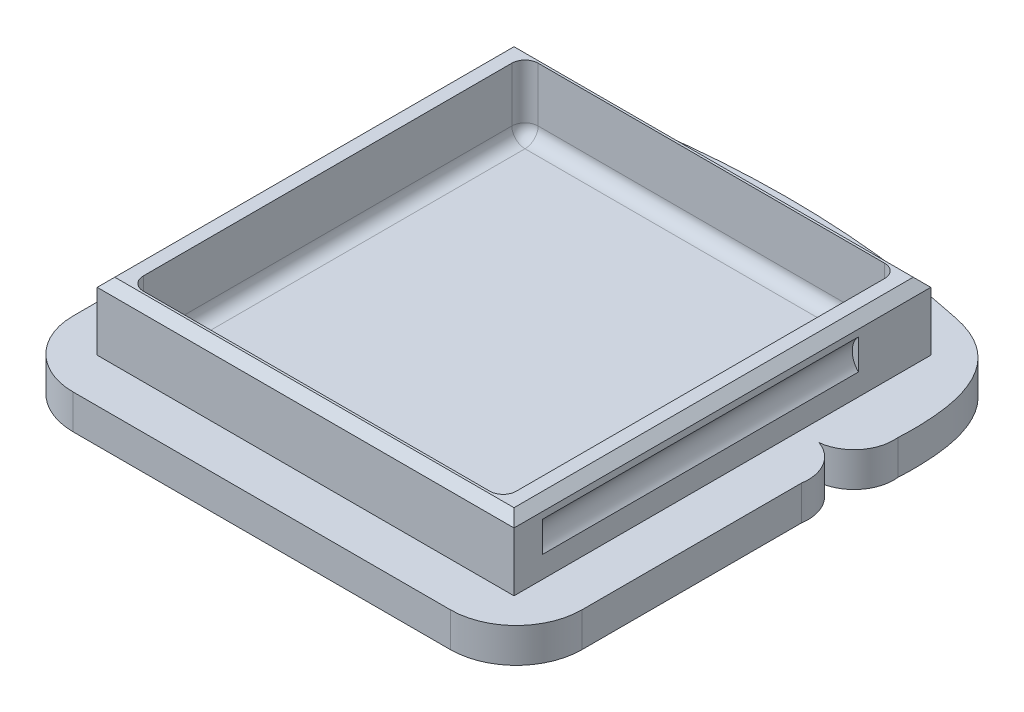
SolidWorks part; units mm, degrees
material "Oak"
ref_plane "Front Plane" through (0, 0, 0) normal (0, 0, 1) x (1, 0, 0)
ref_plane "Top Plane" through (0, 0, 0) normal (0, 1, 0) x (1, 0, 0)
ref_plane "Right Plane" through (0, 0, 0) normal (1, 0, 0) x (0, 0, -1)
sketch "Sketch2" plane through (0, 0, 0) normal (0, 1, 0) x (1, 0, 0)
  line L0 (-66.04, 22.225) -> (66.04, 22.225)
  line L1 (63.5, -66.675) -> (-63.5, -66.675)
  line L2 (63.5, -66.675) -> (63.5, 66.675)
  line L3 (63.5, 66.675) -> (-63.5, 66.675)
  line L4 (-63.5, -66.675) -> (-63.5, 66.675)
  line L5 (63.5, -66.675) -> (-63.5, 66.675) construction
  line L6 (63.5, 66.675) -> (-63.5, -66.675) construction
  line L7 (-73.66, 9.525) -> (-73.66, -53.975)
  line L8 (-54.61, -73.025) -> (54.61, -73.025)
  line L9 (73.66, -53.975) -> (73.66, 9.525)
  line L10 (-73.66, 9.525) -> (-73.66, 13.1711)
  arc A0 (-73.66, 9.525) -> (-66.04, 22.225) centre (-62.3051, 11.348) cw
  arc A1 (73.66, 9.525) -> (66.04, 22.225) centre (62.3051, 11.348) ccw
  arc A2 (-66.04, 22.225) -> (-76.2, 34.925) centre (-64.77, 33.655) cw
  arc A3 (66.04, 22.225) -> (76.2, 34.925) centre (64.77, 33.655) ccw
  arc A4 (-54.2615, 73.3341) -> (54.2615, 73.3341) centre (0, -178.2209) cw
  arc A5 (73.66, -53.975) -> (54.61, -73.025) centre (54.61, -53.975) cw
  arc A6 (-73.66, -53.975) -> (-54.61, -73.025) centre (-54.61, -53.975) ccw
  spline S0 degree 2 poles (-54.2615, 73.3341) (-78.0337, 68.7721) (-76.2, 34.925) knots 0 0 0 1 1 1
  spline S1 degree 2 poles (54.2615, 73.3341) (78.0337, 68.7721) (76.2, 34.925) knots 0 0 0 1 1 1
  point P0 (0, 0)
  dimension "D11" = 11.5003
  dimension "D12" = 11.5003
  dimension "D14" = 11.5003
  dimension "D15" = 11.5003
  dimension "D17" = 19.05
  dimension "D1" = 133.35
  dimension "D2" = 127
  dimension "D3" = 44.45
  dimension "D4" = 2.54
  dimension "D5" = 2.54
  dimension "D6" = 10.16
  dimension "D7" = 10.16
  dimension "D8" = 6.35
  dimension "D9" = 12.7
  dimension "D10" = 12.7
  dimension "D13" = 12.7
extrude "Boss-Extrude1" add sketch "Sketch2" along normal blind 10 contours L7 A6 L8 A5 L9 A1 L0 L2 L1 L4 A0 L10 | L4 L1 L2 L0 | L4 L0 L2 | A2 L0 L4 L10 | S1 A4 S0 L10 L4 L3 L2 | L4 L2 L3 | L0 A3 L2 region at (-72.4781, 0, -27.4885) region at (-64.77, 0, -20.4695) region at (0, 0, -44.45) region at (0, 0, 22.225)
sketch "Sketch3" plane through (0, 10, 0) normal (0, 1, 0) x (1, 0, 0)
  line L1 (-53.975, 57.15) -> (53.975, 57.15)
  line L2 (-53.975, 57.15) -> (-53.975, -57.15)
  line L3 (-53.975, -57.15) -> (53.975, -57.15)
  line L4 (53.975, 57.15) -> (53.975, -57.15)
  line L5 (-53.975, 57.15) -> (53.975, -57.15) construction
  line L6 (-53.975, -57.15) -> (53.975, 57.15) construction
  line L8 (-60.325, 60.325) -> (60.325, 60.325)
  line L9 (-60.325, 60.325) -> (-60.325, -60.325)
  line L10 (-60.325, -60.325) -> (60.325, -60.325)
  line L11 (60.325, 60.325) -> (60.325, -60.325)
  line L12 (-60.325, 60.325) -> (60.325, -60.325) construction
  line L13 (-60.325, -60.325) -> (60.325, 60.325) construction
  point P0 (0, 0)
  point P10 (0, 0)
  dimension "D1" = 107.95
  dimension "D2" = 114.3
  dimension "D3" = 6.35
  dimension "D4" = 3.175
extrude "Boss-Extrude2" add sketch "Sketch3" along normal blind 19.558
fillet "Fillet2" radius 3.81 4 edges at (53.975, 10, 0) (0, 10, -57.15) (-53.975, 10, 0) (0, 10, 57.15)
sketch "Sketch5" plane through (0, 0, 0) normal (0, 0, 1) x (1, 0, 0)
  line L2 (60.325, 25.0747) -> (60.325, 16.2613)
  line L4 (-60.325, 25.0747) -> (-60.325, 16.2613)
  arc A0 (60.325, 25.0747) -> (60.325, 16.2613) centre (64.897, 20.668) ccw
  arc A1 (-60.325, 25.0747) -> (-60.325, 16.2613) centre (-64.897, 20.668) cw
  dimension "D2" = 12.7
extrude "Cut-Extrude2" cut sketch "Sketch5" against normal blind 39.37 and the other way blind 52.07
fillet "Fillet3" radius 3.81 8 edges at (52.8591, 11.1159, 56.0341) (52.8591, 11.1159, -56.0341) (-52.8591, 11.1159, -56.0341) (-52.8591, 11.1159, 56.0341) (53.975, 21.684, 57.15) (53.975, 21.684, -57.15) (-53.975, 21.684, -57.15) (-53.975, 21.684, 57.15)
chamfer "Chamfer1" distance 2.54 angle 45 4 edges at (0, 29.558, 60.325) (-60.325, 29.558, 0) (0, 29.558, -60.325) (60.325, 29.558, 0)
